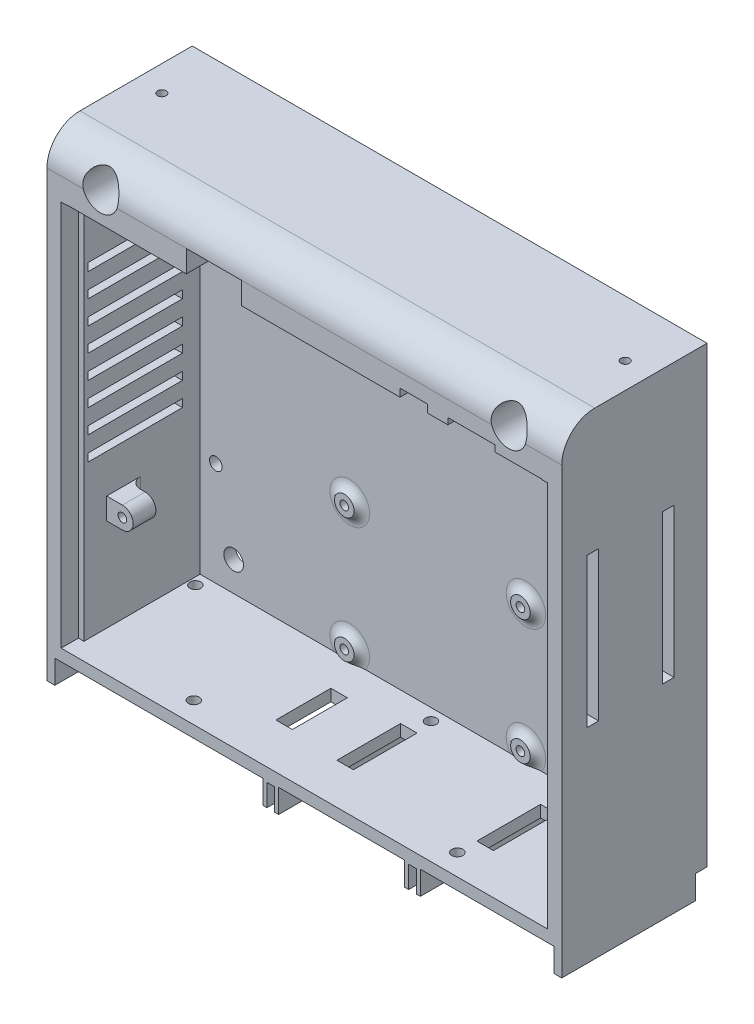
SolidWorks part; units mm, degrees
material "ABS"
ref_plane "Alzado" through (0, 0, 0) normal (0, 0, 1) x (1, 0, 0)
ref_plane "Planta" through (0, 0, 0) normal (0, 1, 0) x (1, 0, 0)
ref_plane "Vista lateral" through (0, 0, 0) normal (1, 0, 0) x (0, 0, -1)
sketch "Croquis1" plane through (0, 0, 0) normal (0, 0, 1) x (1, 0, 0)
  line L1 (0, 0) -> (131.1, 0)
  line L2 (0, 0) -> (0, 109.5)
  line L3 (0, 109.5) -> (131.1, 109.5)
  line L4 (131.1, 0) -> (131.1, 109.5)
  dimension "D1" = 131.1
  dimension "D2" = 109.5
extrude "Saliente-Extruir2" add sketch "Croquis1" along normal blind 39
sketch "Croquis2" plane through (0, 0, 39) normal (0, 0, 1) x (1, 0, 0)
  line L0 (5, 101.5) -> (35.5, 101.5)
  line L1 (126.1, 101.5) -> (126.1, 3)
  line L2 (126.1, 3) -> (5, 3)
  line L3 (5, 3) -> (5, 101.5)
  line L4 (0, 109.5) -> (0, 0) construction
  line L5 (131.1, 0) -> (131.1, 109.5) construction
  line L6 (131.1, 109.5) -> (0, 109.5) construction
  line L7 (0, 0) -> (131.1, 0) construction
  line L8 (96.9, 101.5) -> (96.9, 103.5)
  line L9 (96.9, 103.5) -> (89.9, 103.5)
  line L10 (89.9, 103.5) -> (89.9, 101.5)
  line L11 (96.9, 101.5) -> (102.1, 101.5)
  line L12 (102.1, 101.5) -> (102.1, 103.1)
  line L13 (102.1, 103.1) -> (114.1, 103.1)
  line L14 (114.1, 103.1) -> (114.1, 101.5)
  line L15 (114.1, 101.5) -> (126.1, 101.5)
  line L17 (35.5, 101.5) -> (35.5, 107.1)
  line L18 (35.5, 107.1) -> (49.5, 107.1)
  line L19 (49.5, 107.1) -> (49.5, 101.5)
  line L20 (49.5, 101.5) -> (89.9, 101.5)
  point P20 (42.5, 101.5)
  point P24 (42.5, 101.5)
  dimension "D1" = 5
  dimension "D2" = 5
  dimension "D3" = 8
  dimension "D4" = 3
  dimension "D5" = 7
  dimension "D6" = 36.2
  dimension "D7" = 2
  dimension "D8" = 24
  dimension "D9" = 12
  dimension "D10" = 1.6
  dimension "D11" = 37.5
  dimension "D12" = 7
  dimension "D13" = 5.6
extrude "Cortar-Extruir1" cut sketch "Croquis2" against normal blind 36 contours L3 L0 L17 L18 L19 L20 L10 L9 L8 L11 L12 L13 L14 L15 L1 L2
ref_plane "Plano1" through (0, 0, 21) normal (0, 0, 1) x (1, 0, 0)
sketch "Croquis3" plane through (0, 0, 3) normal (0, 0, 1) x (1, 0, 0)
  line L0 (5, 101.5) -> (126.1, 101.5) construction
  line L1 (5, 101.5) -> (5, 3) construction
  line L2 (65.55, 101.5) -> (65.55, 3) construction
  line L3 (126.1, 3) -> (5, 3) construction
  line L5 (122.1, 26.65) -> (126.1, 26.65)
  line L6 (126.1, 101.5) -> (126.1, 3) construction
  line L7 (122.1, 32.15) -> (126.1, 32.15)
  line L8 (126.1, 101.5) -> (126.1, 3) construction
  line L9 (126.1, 32.15) -> (126.1, 26.65)
  line L10 (122.1, 94.75) -> (126.1, 94.75)
  line L11 (122.1, 100.25) -> (126.1, 100.25)
  line L12 (126.1, 100.25) -> (126.1, 94.75)
  line L13 (9, 100.25) -> (5, 100.25)
  line L14 (9, 94.75) -> (5, 94.75)
  line L15 (5, 94.75) -> (5, 100.25)
  line L16 (9, 26.65) -> (5, 26.65)
  line L17 (9, 32.15) -> (5, 32.15)
  line L18 (5, 32.15) -> (5, 26.65)
  circle A0 centre (9, 97.5) radius 2.75
  circle A1 centre (9, 97.5) radius 1.1
  circle A2 centre (122.1, 97.5) radius 2.75
  circle A3 centre (122.1, 97.5) radius 1.1
  circle A4 centre (9, 29.4) radius 2.75
  circle A5 centre (9, 29.4) radius 1.1
  circle A6 centre (122.1, 29.4) radius 2.75
  circle A7 centre (122.1, 29.4) radius 1.1
  point P16 (5, 25.4)
  line M10 (126.1, 3) -> (126.1, 101.5)
  line M20 (5, 101.5) -> (5, 3)
  dimension "D1" = 4
  dimension "D2" = 5.5
  dimension "D4" = 2.2
  dimension "D3" = 4
  dimension "D5" = 76.1
  dimension "D6" = 4
extrude "Saliente-Extruir6" add sketch "Croquis3" along normal blind 5.8 from surface contours A0 A1 | A0 L13 L14 M20 | A2 A3 | L11 A2 L10 M10 | A6 A7 | A6 L5 L7 M10 | A4 A5 | A4 L17 L16 M20 region at (125.0776, 29.4, 3) region at (125.0776, 97.5, 3) region at (119.4278, 29.4, 3) region at (119.4278, 97.5, 3) region at (6.0224, 97.5, 3) region at (6.0224, 29.4, 3) region at (10.8895, 99.3895, 3) region at (10.8895, 31.2895, 3) starting at plane "Plano1"
fillet "Redondeo1" radius 2.8 4 edges at (126.1, 97.5, 21) (126.1, 29.4, 21) (5, 97.5, 21) (5, 29.4, 21)
sketch "Croquis4" plane through (0, 0, 39) normal (0, 0, 1) x (1, 0, 0)
  line L0 (0, 109.5) -> (131.1, 109.5)
  line L1 (131.1, 109.5) -> (131.1, 115.5)
  line L2 (131.1, 115.5) -> (0, 115.5)
  line L3 (0, 115.5) -> (0, 109.5)
  dimension "D1" = 6
extrude "Saliente-Extruir7" add sketch "Croquis4" against normal up to vertex (39 mm away) contours L3 L0 L1 L2 up to point (0, 109.5, 0)
sketch "Croquis5" plane through (0, 0, 0) normal (-1, 0, 0) x (0, 0, 1)
  line L0 (19.5, 0) -> (19.5, 115.5) construction
  line L1 (39, 0) -> (0, 0) construction
  line L2 (0, 115.5) -> (39, 115.5) construction
  line L3 (7.5, 48) -> (7.5, 50)
  line L4 (7.5, 42) -> (31.5, 42)
  line L5 (7.5, 42) -> (7.5, 44)
  line L6 (7.5, 44) -> (31.5, 44)
  line L7 (31.5, 42) -> (31.5, 44)
  line L8 (7.5, 42) -> (31.5, 44) construction
  line L9 (7.5, 44) -> (31.5, 42) construction
  line L10 (7.5, 48) -> (31.5, 48)
  line L11 (31.5, 48) -> (31.5, 50)
  line L12 (7.5, 50) -> (31.5, 50)
  line L13 (7.5, 54) -> (7.5, 56)
  line L14 (7.5, 54) -> (31.5, 54)
  line L15 (31.5, 54) -> (31.5, 56)
  line L16 (7.5, 56) -> (31.5, 56)
  line L17 (7.5, 60) -> (7.5, 62)
  line L18 (7.5, 60) -> (31.5, 60)
  line L19 (31.5, 60) -> (31.5, 62)
  line L20 (7.5, 62) -> (31.5, 62)
  line L21 (7.5, 66) -> (7.5, 68)
  line L22 (7.5, 66) -> (31.5, 66)
  line L23 (31.5, 66) -> (31.5, 68)
  line L24 (7.5, 68) -> (31.5, 68)
  line L25 (7.5, 72) -> (7.5, 74)
  line L26 (7.5, 72) -> (31.5, 72)
  line L27 (31.5, 72) -> (31.5, 74)
  line L28 (7.5, 74) -> (31.5, 74)
  line L29 (7.5, 78) -> (7.5, 80)
  line L30 (7.5, 80) -> (31.5, 80)
  line L31 (31.5, 78) -> (31.5, 80)
  line L32 (7.5, 78) -> (31.5, 78)
  line L33 (7.5, 84) -> (7.5, 86)
  line L34 (7.5, 86) -> (31.5, 86)
  line L35 (31.5, 84) -> (31.5, 86)
  line L36 (7.5, 84) -> (31.5, 84)
  point P6 (19.5, 43)
  dimension "D1" = 24
  dimension "D2" = 2
  dimension "D3" = 42
  dimension "D4" = 6
  dimension "D5" = 3
extrude "Cortar-Extruir3" cut sketch "Croquis5" against normal up to next
sketch "Croquis6" plane through (131.1, 0, 0) normal (1, 0, 0) x (0, 0, -1)
  line L1 (-30.6, 46) -> (-27.6, 46)
  line L2 (-39, 0) -> (0, 0) construction
  line L3 (-30.6, 46) -> (-30.6, 84)
  line L4 (-30.6, 84) -> (-27.6, 84)
  line L5 (-27.6, 84) -> (-27.6, 46)
  line L6 (-19.5, 0) -> (-19.5, 115.5) construction
  line L7 (0, 115.5) -> (-39, 115.5) construction
  line L8 (-8.4, 84) -> (-11.4, 84)
  line L9 (-8.4, 46) -> (-8.4, 84)
  line L10 (-8.4, 46) -> (-11.4, 46)
  line L11 (-11.4, 84) -> (-11.4, 46)
  point P0 (-39, 115.5)
  dimension "D1" = 46
  dimension "D2" = 3
  dimension "D3" = 8.4
  dimension "D4" = 38
extrude "Cortar-Extruir4" cut sketch "Croquis6" against normal up to next
sketch "Croquis7" plane through (0, 0, 3) normal (0, 0, 1) x (1, 0, 0)
  circle A0 centre (122.1, 97.5) radius 1.1 construction
  circle A1 centre (122.1, 29.4) radius 1.1 construction
  circle A2 centre (9, 29.4) radius 1.1 construction
  circle A3 centre (9, 97.5) radius 1.1 construction
  circle A4 centre (122.1, 97.5) radius 1.1
  circle A5 centre (122.1, 29.4) radius 1.1
  circle A6 centre (9, 29.4) radius 1.1
  circle A7 centre (9, 97.5) radius 1.1
  circle A8 centre (9, 97.5) radius 1.6
  circle A9 centre (122.1, 97.5) radius 1.6
  circle A10 centre (122.1, 29.4) radius 1.6
  circle A11 centre (9, 29.4) radius 1.6
  dimension "D1" = 3.2
extrude "Cortar-Extruir5" cut sketch "Croquis7" against normal blind 10 contours A8 A7 | A7 | A4 | A9 A4 | A10 A5 | A5 | A6 | A11 A6 region at (122.1, 97.5, 3) region at (122.1, 29.4, 3) region at (9, 29.4, 3) region at (9, 97.5, 3) region at (7.4453, 97.5, 3) region at (120.5453, 97.5, 3) region at (120.5453, 29.4, 3) region at (7.4453, 29.4, 3)
sketch "Croquis9" plane through (0, 0, 39) normal (0, 0, 1) x (1, 0, 0)
  line L4 (0, 115.5) -> (0, 0)
  line L5 (0, 0) -> (131.1, 0)
  line L6 (131.1, 0) -> (131.1, 115.5)
  line L7 (131.1, 115.5) -> (0, 115.5)
  line L8 (0, 115.5) -> (0, 0)
  line L9 (0, 0) -> (131.1, 0)
  line L10 (131.1, 0) -> (131.1, 115.5)
  line L11 (131.1, 115.5) -> (0, 115.5)
  dimension "D1" = 0
extrude "Cortar-Extruir6" cut sketch "Croquis9" against normal blind 2
sketch "Croquis10" plane through (0, 0, 37) normal (0, 0, 1) x (1, 0, 0)
  line L0 (65.55, 0) -> (65.55, 115.5) construction
  line L1 (5, 3) -> (3.6, 3)
  line L2 (5, 3) -> (5, 101.3878)
  line L3 (5, 101.3878) -> (3.6, 101.3878)
  line L4 (3.6, 3) -> (3.6, 101.3878)
  line L5 (0, 0) -> (131.1, 0) construction
  line L6 (131.1, 115.5) -> (0, 115.5) construction
  line L7 (126.1, 101.3878) -> (127.5, 101.3878)
  line L8 (127.5, 3) -> (127.5, 101.3878)
  line L9 (126.1, 3) -> (127.5, 3)
  line L10 (126.1, 3) -> (126.1, 101.3878)
  dimension "D1" = 1.4
extrude "Cortar-Extruir7" cut sketch "Croquis10" against normal blind 4.4
sketch "Croquis12" plane through (0, 0, 37) normal (0, 0, 1) x (1, 0, 0)
  line L0 (65.55, 115.5) -> (65.55, 85.6878) construction
  line L1 (131.1, 115.5) -> (0, 115.5) construction
  line L2 (25.0028, 101.5) -> (25.0028, 115.5) construction
  line L3 (35.5, 101.5) -> (5, 101.5) construction
  circle A0 centre (13.55, 108.5) radius 4.5
  circle A1 centre (117.55, 108.5) radius 4.5
  circle A2 centre (13.55, 10.5) radius 4.5
  circle A3 centre (117.55, 10.5) radius 4.5
  point P6 (25.0028, 108.5)
  dimension "D1" = 9
  dimension "D2" = 52
  dimension "D3" = 2
sketch "Croquis13" plane through (0, 0, 37) normal (0, 0, 1) x (1, 0, 0)
  circle A0 centre (13.55, 108.5) radius 2.5
  circle A1 centre (117.55, 108.5) radius 2.5
  circle A2 centre (13.55, 10.5) radius 2.5
  circle A3 centre (117.55, 10.5) radius 2.5
  dimension "D1" = 5
extrude "Cortar-Extruir9" cut sketch "Croquis13" against normal up to next
extrude "Cortar-Extruir10" cut sketch "Croquis12" against normal blind 33
fillet "Redondeo3" radius 8.4 1 edges at (65.55, 115.5, 37)
sketch "Croquis14" plane through (0, 115.5, 0) normal (0, 1, 0) x (1, 0, 0)
  line L0 (65.55, 0) -> (65.55, -28.6) construction
  line L1 (131.1, 0) -> (0, 0) construction
  line L2 (0, -28.6) -> (131.1, -28.6) construction
  circle A0 centre (6.55, -14.3) radius 2.2
  circle A1 centre (124.55, -14.3) radius 2.2
  point P9 (65.55, -14.3)
  dimension "D1" = 4.4
  dimension "D2" = 59
sketch "Croquis15" plane through (0, 115.5, 0) normal (0, 1, 0) x (1, 0, 0)
  line L0 (65.55, 0) -> (65.55, -29.7725) construction
  line L1 (131.1, 0) -> (0, 0) construction
  circle A0 centre (6.55, -14.3) radius 1.1
  circle A1 centre (124.55, -14.3) radius 1.1
  dimension "D1" = 2.2
extrude "Cortar-Extruir11" cut sketch "Croquis15" against normal up to next
sketch "Croquis16" plane through (0, 0, 3) normal (0, 0, 1) x (1, 0, 0)
  line L0 (65.55, 0) -> (65.55, 42.1815) construction
  line L1 (0, 0) -> (131.1, 0) construction
  line L2 (39.95, 3) -> (91.15, 3)
  line L3 (126.1, 3) -> (5, 3) construction
  line L4 (91.15, 3) -> (91.15, 41.1)
  line L5 (91.15, 41.1) -> (39.95, 41.1)
  line L6 (39.95, 41.1) -> (39.95, 3)
  circle A0 centre (87.98, 6.17) radius 1.1
  circle A1 centre (43.12, 6.17) radius 1.1
  circle A2 centre (87.98, 37.93) radius 1.1
  circle A3 centre (43.12, 37.93) radius 1.1
  point P9 (65.55, 3)
  point P19 (65.55, 21.0907)
  dimension "D3" = 2.2
  dimension "D6" = 3.17
  dimension "D1" = 51.2
  dimension "D2" = 38.1
  dimension "D4" = 3.17
  dimension "D5" = 3.17
  dimension "D7" = 3.17
extrude "Cortar-Extruir13" cut sketch "Croquis16" against normal up to next contours A3 | A2 | A0 | A1 region at (87.98, 6.17, 3) region at (43.12, 6.17, 3) region at (87.98, 37.93, 3) region at (43.12, 37.93, 3)
sketch "Croquis17" plane through (0, 0, 3) normal (0, 0, 1) x (1, 0, 0)
  circle A0 centre (43.12, 6.17) radius 1.1 construction
  circle A1 centre (87.98, 6.17) radius 1.1 construction
  circle A2 centre (87.98, 37.93) radius 1.1 construction
  circle A3 centre (43.12, 37.93) radius 1.1 construction
  circle A4 centre (43.12, 6.17) radius 1.1
  circle A5 centre (87.98, 6.17) radius 1.1
  circle A6 centre (87.98, 37.93) radius 1.1
  circle A7 centre (43.12, 37.93) radius 1.1
  circle A8 centre (43.12, 37.93) radius 2.5
  circle A9 centre (87.98, 37.93) radius 2.5
  circle A10 centre (87.98, 6.17) radius 2.5
  circle A11 centre (43.12, 6.17) radius 2.5
  dimension "D1" = 5
extrude "Saliente-Extruir8" add sketch "Croquis17" along normal blind 1.4
fillet "Redondeo4" radius 3 4 edges at (85.48, 37.93, 3) (85.48, 6.17, 3) (40.62, 6.17, 3) (40.62, 37.93, 3)
sketch "Croquis18" plane through (0, 0, 0) normal (0, -1, 0) x (1, 0, 0)
  line L0 (0, 18.5) -> (131.1, 18.5) construction
  line L1 (0, 37) -> (0, 0) construction
  line L2 (131.1, 37) -> (131.1, 0) construction
  line L4 (63.45, 10.4) -> (67.65, 10.4)
  line L5 (63.45, 10.4) -> (63.45, 26.6)
  line L6 (63.45, 26.6) -> (67.65, 26.6)
  line L7 (67.65, 10.4) -> (67.65, 26.6)
  line L8 (63.45, 10.4) -> (67.65, 26.6) construction
  line L9 (63.45, 26.6) -> (67.65, 10.4) construction
  line L10 (46.8, 11.5) -> (51, 11.5)
  line L11 (46.8, 11.5) -> (46.8, 25.5)
  line L12 (46.8, 25.5) -> (51, 25.5)
  line L13 (51, 11.5) -> (51, 25.5)
  line L14 (46.8, 11.5) -> (51, 25.5) construction
  line L15 (46.8, 25.5) -> (51, 11.5) construction
  line L16 (99.1, 10.4) -> (103.3, 10.4)
  line L17 (99.1, 10.4) -> (99.1, 26.6)
  line L18 (99.1, 26.6) -> (103.3, 26.6)
  line L19 (103.3, 10.4) -> (103.3, 26.6)
  line L20 (99.1, 10.4) -> (103.3, 26.6) construction
  line L21 (99.1, 26.6) -> (103.3, 10.4) construction
  point P6 (65.55, 18.5)
  point P11 (57, 18.5)
  point P12 (93.1, 18.5)
  point P13 (48.9, 18.5)
  point P18 (101.2, 18.5)
  dimension "D1" = 4.2
  dimension "D2" = 16.2
  dimension "D3" = 57
  dimension "D4" = 38
  dimension "D5" = 4.2
  dimension "D6" = 14
  dimension "D7" = 6
  dimension "D8" = 4.2
  dimension "D9" = 6
extrude "Cortar-Extruir14" cut sketch "Croquis18" against normal up to next
sketch "Croquis19" plane through (0, 0, 37) normal (0, 0, 1) x (1, 0, 0)
  line L0 (0, 0) -> (57, 0)
  line L1 (0, 0) -> (131.1, 0) construction
  line L2 (57, 0) -> (57, -6)
  line L3 (57, -6) -> (55, -6)
  line L4 (55, -6) -> (55, 0)
  line L5 (0, 0) -> (0, -6)
  line L6 (0, -6) -> (2, -6)
  line L7 (2, -6) -> (2, 0)
  line L8 (131.1, 0) -> (93.1, 0)
  line L9 (93.1, 0) -> (93.1, -6)
  line L10 (93.1, -6) -> (95.1, -6)
  line L11 (95.1, -6) -> (95.1, 0)
  line L12 (131.1, 0) -> (131.1, -6)
  line L13 (131.1, -6) -> (129.1, -6)
  line L14 (129.1, -6) -> (129.1, 0)
  line L15 (57, -6) -> (59, -6)
  line L16 (59, -6) -> (59, 0)
  line L17 (59, 0) -> (91.1, 0)
  line L18 (91.1, 0) -> (91.1, -6)
  line L19 (91.1, -6) -> (93.1, -6)
  line M31 (0, 0) -> (131.1, 0)
  dimension "D1" = 57
  dimension "D2" = 2
  dimension "D3" = 6
  dimension "D4" = 38
  dimension "D5" = 2
  dimension "D6" = 2
extrude "Saliente-Extruir10" add sketch "Croquis19" against normal up to vertex (34 mm away) contours L6 L7 L5 M31 | L4 L3 L2 L0 | L15 L16 L2 M31 | L14 L13 L12 M31 | L10 L11 L9 M31 | L18 L19 L9 M31 region at (130.1, -3, 37) region at (92.1, -3, 37) region at (56, -3, 37) region at (1, -3, 37) region at (58, -3, 37) region at (94.1, -3, 37) up to point (84.0647, 3, 3)
sketch "Croquis20" plane through (0, 0, 37) normal (0, 0, 1) x (1, 0, 0)
  line L0 (57, -6) -> (58, -6)
  line L1 (59, -6) -> (55, -6) construction
  line L2 (58, -6) -> (58, -0.4)
  line L3 (58, -0.4) -> (56, -0.4)
  line L4 (56, -0.4) -> (56, -6)
  line L5 (56, -6) -> (57, -6)
  line L6 (93.1, -6) -> (94.1, -6)
  line L7 (91.1, -6) -> (95.1, -6) construction
  line L8 (94.1, -6) -> (94.1, -0.4)
  line L9 (94.1, -0.4) -> (92.1, -0.4)
  line L10 (92.1, -0.4) -> (92.1, -6)
  line L11 (92.1, -6) -> (93.1, -6)
  dimension "D1" = 1
  dimension "D2" = 5.6
  dimension "D3" = 2
  dimension "D4" = 1
  dimension "D5" = 1
  dimension "D6" = 5.6
extrude "Cortar-Extruir15" cut sketch "Croquis20" against normal up to next
ref_plane "Plano2" through (102.1, 101.5, 37) normal (0, -1, 0) x (-1, 0, 0)
sketch "Croquis22" plane through (0, 0, 0) normal (0, -1, 0) x (1, 0, 0)
  line L0 (0, 6) -> (131.1, 6) construction
  line L3 (0, 3) -> (0, 37) construction
  line L4 (131.1, 3) -> (131.1, 37) construction
  line L5 (0, 31.6) -> (131.1, 31.6) construction
  line L6 (2, 37) -> (55, 37) construction
  circle A0 centre (6.8, 6) radius 1.4
  circle A1 centre (66.8, 6) radius 1.4
  circle A3 centre (124.3, 6) radius 1.4
  circle A4 centre (32, 31.6) radius 1.4
  circle A5 centre (99.1, 31.6) radius 1.4
  point P4 (6.8, 6)
  dimension "D3" = 2.8
  dimension "D1" = 6
  dimension "D2" = 6.8
  dimension "D4" = 60
  dimension "D5" = 6.8
  dimension "D7" = 5.4
  dimension "D8" = 32
  dimension "D9" = 32
extrude "Cortar-Extruir19" cut sketch "Croquis22" against normal up to surface (3 mm away) up to face at (101.2, 3, 18.5)
